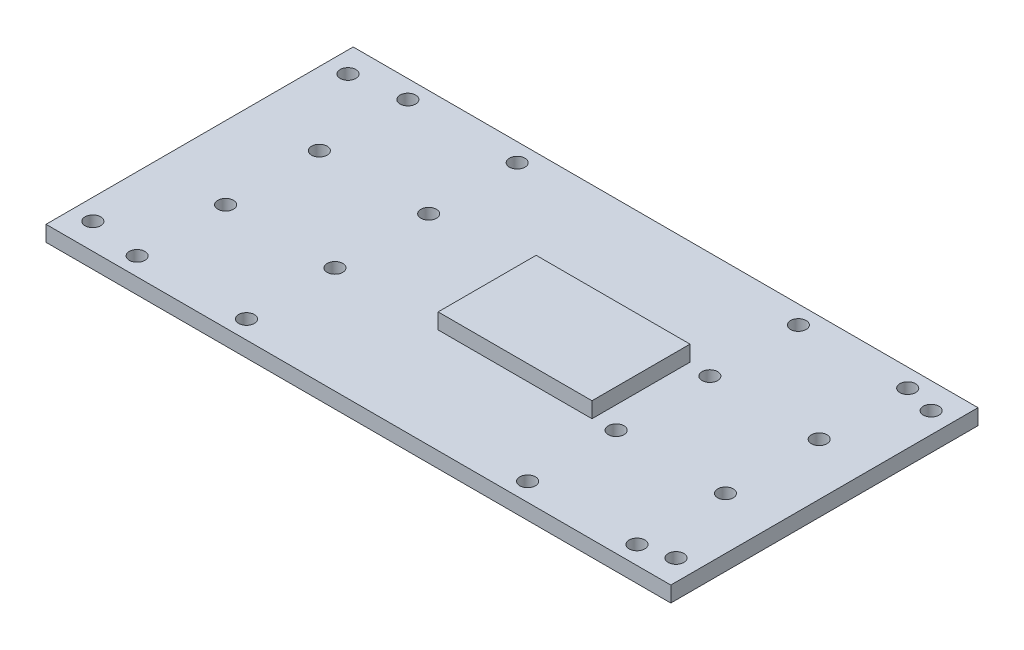
SolidWorks part; units mm, degrees
ref_plane "Front Plane" through (0, 0, 0) normal (0, 0, 1) x (1, 0, 0)
ref_plane "Top Plane" through (0, 0, 0) normal (0, 1, 0) x (1, 0, 0)
ref_plane "Right Plane" through (0, 0, 0) normal (1, 0, 0) x (0, 0, -1)
sketch "Sketch1" plane through (0, 0, 0) normal (0, 1, 0) x (1, 0, 0)
  line L0 (56, 24.5) -> (56, -24.5) construction
  line L1 (-60, -29.5) -> (60, -29.5)
  line L2 (-60, -29.5) -> (-60, 29.5)
  line L3 (-60, 29.5) -> (60, 29.5)
  line L4 (60, -29.5) -> (60, 29.5)
  line L5 (-60, -29.5) -> (60, 29.5) construction
  line L6 (-60, 29.5) -> (60, -29.5) construction
  line L7 (-46, 26) -> (-25, 26) construction
  line L8 (-46, 26) -> (-46, 9) construction
  line L9 (-46, 9) -> (-25, 9) construction
  line L10 (-25, 26) -> (-25, 9) construction
  line L11 (29, 26) -> (50, 26) construction
  line L12 (29, 26) -> (29, 9) construction
  line L13 (29, 9) -> (50, 9) construction
  line L14 (50, 26) -> (50, 9) construction
  line L15 (29, -9) -> (50, -9) construction
  line L16 (29, -9) -> (29, -26) construction
  line L17 (29, -26) -> (50, -26) construction
  line L18 (50, -9) -> (50, -26) construction
  line L19 (-46, -9) -> (-25, -9) construction
  line L20 (-46, -9) -> (-46, -26) construction
  line L21 (-46, -26) -> (-25, -26) construction
  line L22 (-25, -9) -> (-25, -26) construction
  line L23 (29, 9) -> (29, -9) construction
  line L24 (56, -24.5) -> (-56, -24.5) construction
  line L25 (-56, -24.5) -> (-56, 24.5) construction
  line L26 (-56, 24.5) -> (56, 24.5) construction
  circle A0 centre (-25, 26) radius 1.5
  circle A1 centre (-46, 26) radius 1.5
  circle A2 centre (-46, 9) radius 1.5
  circle A3 centre (-25, 9) radius 1.5
  circle A4 centre (-25, -9) radius 1.5
  circle A5 centre (-46, -9) radius 1.5
  circle A6 centre (-25, -26) radius 1.5
  circle A7 centre (-46, -26) radius 1.5
  circle A8 centre (50, 26) radius 1.5
  circle A9 centre (29, 26) radius 1.5
  circle A10 centre (29, -9) radius 1.5
  circle A11 centre (50, -9) radius 1.5
  circle A12 centre (50, -26) radius 1.5
  circle A13 centre (29, -26) radius 1.5
  circle A14 centre (50, 9) radius 1.5
  circle A15 centre (29, 9) radius 1.5
  circle A20 centre (56, -24.5) radius 1.5
  circle A21 centre (56, 24.5) radius 1.5
  circle A22 centre (-56, 24.5) radius 1.5
  circle A23 centre (-56, -24.5) radius 1.5
  point P0 (0, 0)
  point P36 (29, 0)
  point P47 (60, 0)
  point P48 (56, 0)
  point P49 (0, -29.5)
  point P50 (0, -24.5)
  dimension "D5" = 3
  dimension "D9" = 3
  dimension "D1" = 75
  dimension "D2" = 35
  dimension "D3" = 21
  dimension "D4" = 17
  dimension "D6" = 59
  dimension "D7" = 10
  dimension "D8" = 120
  dimension "D10" = 5
  dimension "D11" = 4
extrude "Boss-Extrude1" add sketch "Sketch1" along normal blind 3
sketch "Sketch2" plane through (0, 3, 0) normal (0, 1, 0) x (1, 0, 0)
  line L0 (60, -29.5) -> (60, 29.5) construction
  line L1 (-4.7746, -9.4125) -> (24.7746, -9.4125)
  line L2 (-4.7746, -9.4125) -> (-4.7746, 9.4125)
  line L3 (-4.7746, 9.4125) -> (24.7746, 9.4125)
  line L4 (24.7746, -9.4125) -> (24.7746, 9.4125)
  line L5 (-4.7746, -9.4125) -> (24.7746, 9.4125) construction
  line L6 (-4.7746, 9.4125) -> (24.7746, -9.4125) construction
  point P0 (10, 0)
  dimension "D1" = 50
extrude "Boss-Extrude2" add sketch "Sketch2" along normal blind 3
